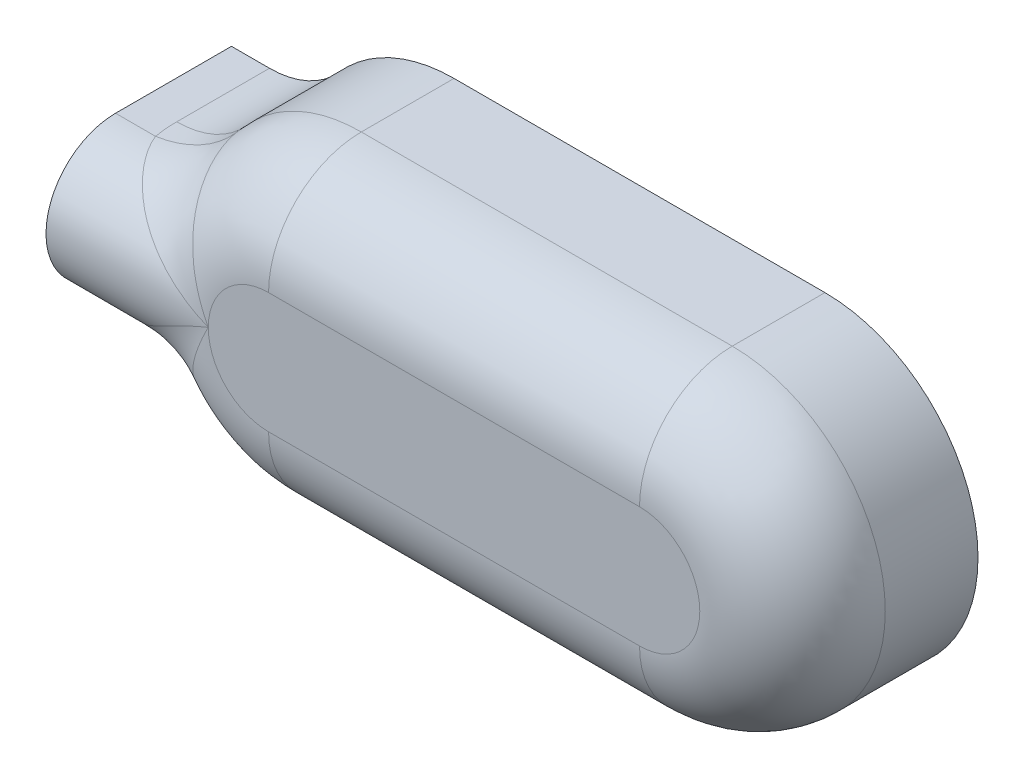
SolidWorks part; units mm, degrees
ref_plane "Front Plane" through (0, 0, 0) normal (0, 0, 1) x (1, 0, 0)
ref_plane "Top Plane" through (0, 0, 0) normal (0, 1, 0) x (1, 0, 0)
ref_plane "Right Plane" through (0, 0, 0) normal (1, 0, 0) x (0, 0, -1)
sketch "Sketch1" plane through (0, 0, 0) normal (0, 0, 1) x (1, 0, 0)
  line L0 (77.2984, 53.6856) -> (117.2984, 53.6856) construction
  line L1 (77.2984, 67.1856) -> (117.2984, 67.1856) construction
  line L2 (77.2984, 40.1856) -> (117.2984, 40.1856) construction
  line L3 (117.2984, 53.6856) -> (77.2984, 53.6856) construction
  line L4 (117.2984, 37.1856) -> (77.2984, 37.1856)
  line L5 (117.2984, 70.1856) -> (77.2984, 70.1856)
  arc A0 (77.2984, 67.1856) -> (77.2984, 40.1856) centre (77.2984, 53.6856) ccw construction
  arc A1 (117.2984, 40.1856) -> (117.2984, 67.1856) centre (117.2984, 53.6856) ccw construction
  arc A4 (117.2984, 37.1856) -> (117.2984, 70.1856) centre (117.2984, 53.6856) ccw
  arc A5 (77.2984, 70.1856) -> (77.2984, 37.1856) centre (77.2984, 53.6856) ccw
  point P3 (97.2984, 53.6856)
  point P16 (97.2984, 53.6856)
  dimension "D1" = 3
extrude "Boss-Extrude1" add sketch "Sketch1" along normal blind 20
sketch "Sketch2" plane through (0, 0, 0) normal (1, 0, 0) x (0, 0, -1)
  line L0 (-12.5, 53.6856) -> (7.5, 53.6856) construction
  line L1 (-12.5, 61.1856) -> (0, 61.1856)
  line L2 (-12.5, 46.1856) -> (0, 46.1856)
  line L3 (0, 37.1856) -> (0, 70.1856) construction
  line L5 (-20, 70.1856) -> (-20, 37.1856) construction
  line L7 (0, 61.1856) -> (0, 46.1856)
  line L8 (-20, 70.1856) -> (-20, 37.1856) construction
  arc A0 (-12.5, 61.1856) -> (-12.5, 46.1856) centre (-12.5, 53.6856) ccw
  point P2 (-2.5, 53.6856)
  point P4 (0, 0)
  point P10 (-20, 53.6856)
  dimension "D1" = 15
extrude "Boss-Extrude2" add sketch "Sketch2" against normal blind 24 from vertex at 77.2984 starting at point (77.2984, 37.1856, 20)
fillet "Fillet1" radius 10 5 edges at (97.2984, 37.1856, 20) (65.6312, 42.0184, 20) (65.6312, 65.3529, 20) (97.2984, 70.1856, 20) (133.7984, 53.6856, 20)
fillet "Fillet2" radius 10 6 edges at (62.6015, 46.1856, 5) (65.1248, 59.6051, 17.1055) (65.1248, 47.7662, 17.1055) (62.6015, 61.1856, 5)
shell "Shell1" thickness 2
